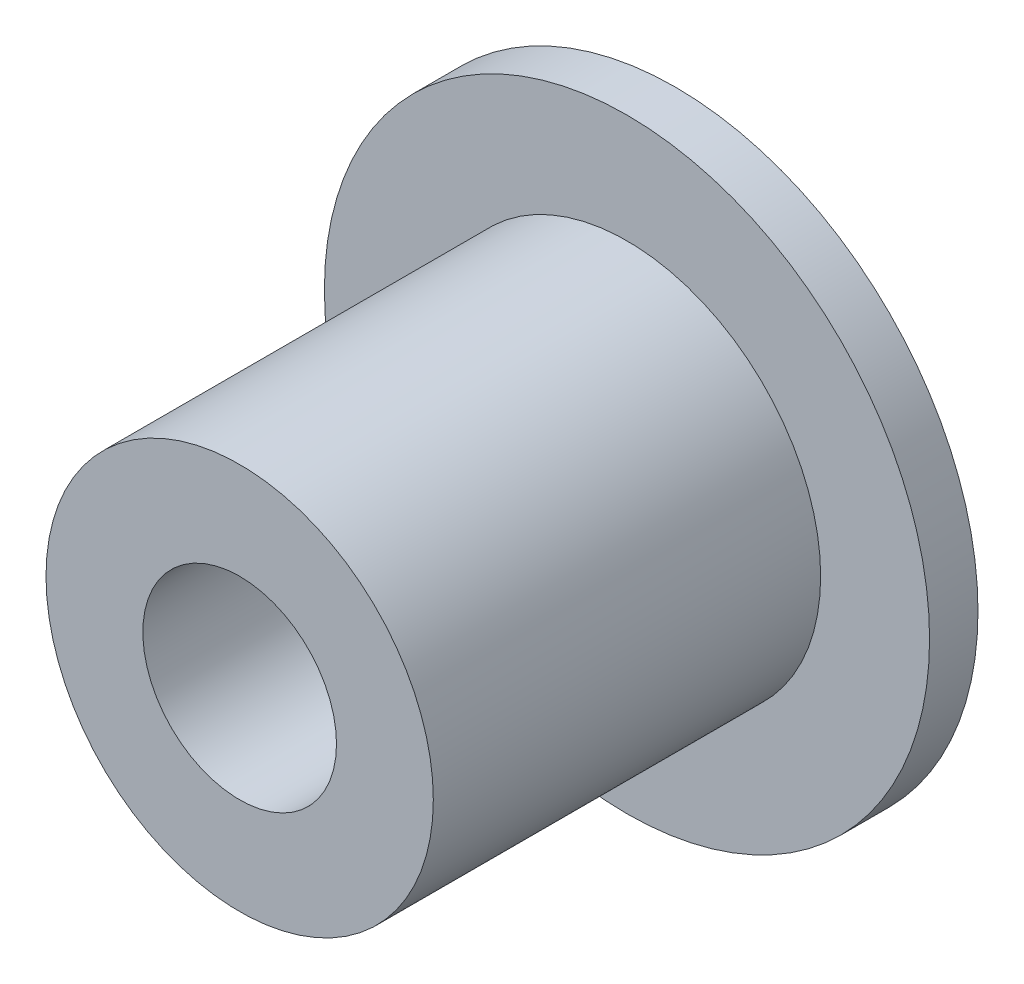
SolidWorks part; units mm, degrees
material "Plain Carbon Steel"
ref_plane "Front Plane" through (0, 0, 0) normal (0, 0, 1) x (1, 0, 0)
ref_plane "Top Plane" through (0, 0, 0) normal (0, 1, 0) x (1, 0, 0)
ref_plane "Right Plane" through (0, 0, 0) normal (1, 0, 0) x (0, 0, -1)
sketch "Sketch1" plane through (0, 0, 0) normal (0, 0, 1) x (1, 0, 0)
  circle A0 centre (0, 0) radius 12.7
  circle A1 centre (0, 0) radius 6.35
  dimension "D1" = 25.4
  dimension "D2" = 12.7
extrude "Boss-Extrude1" add sketch "Sketch1" along normal blind 3.175
sketch "Sketch2" plane through (0, 0, 3.175) normal (0, 0, 1) x (1, 0, 0)
  circle A0 centre (0, 0) radius 6.35 construction
  circle A1 centre (0, 0) radius 6.35
  circle A2 centre (0, 0) radius 19.8438
  dimension "D1" = 39.6875
extrude "Boss-Extrude2" add sketch "Sketch2" along normal blind 3.175
sketch "Sketch3" plane through (0, 0, 6.35) normal (0, 0, 1) x (1, 0, 0)
  circle A0 centre (0, 0) radius 6.35 construction
  circle A1 centre (0, 0) radius 12.7
  circle A2 centre (0, 0) radius 12.7
  circle A3 centre (0, 0) radius 6.35
  dimension "D1" = 0
extrude "Boss-Extrude3" add sketch "Sketch3" along normal blind 25.4
sketch "Sketch4" plane through (0, 0, 0) normal (0, 0, -1) x (-1, 0, 0)
  line L1 (-1.5875, 0) -> (1.5875, 0)
  line L2 (-1.5875, 0) -> (-1.5875, 9.525)
  line L3 (-1.5875, 9.525) -> (1.5875, 9.525)
  line L4 (1.5875, 0) -> (1.5875, 9.525)
  line L5 (-1.5875, 0) -> (1.5875, 9.525) construction
  line L6 (-1.5875, 9.525) -> (1.5875, 0) construction
  point P0 (0, 4.7625)
  dimension "D1" = 3.175
  dimension "D2" = 9.525
extrude "Cut-Extrude1" cut sketch "Sketch4" against normal blind 22.225
